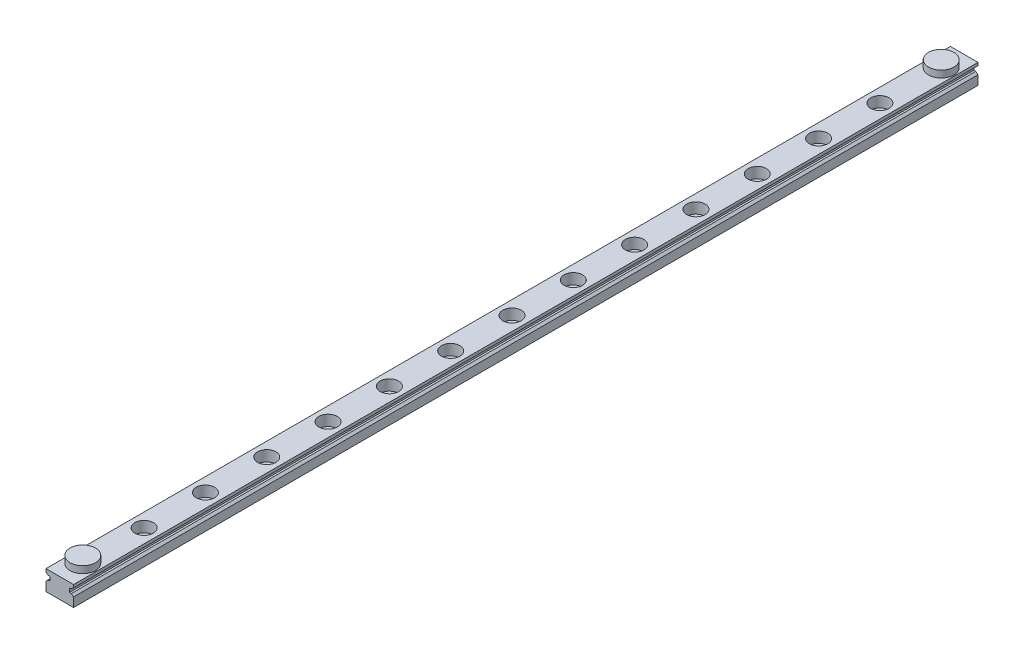
SolidWorks part; units mm, degrees
ref_plane "Front Plane" through (0, 0, 0) normal (0, 0, 1) x (1, 0, 0)
ref_plane "Top Plane" through (0, 0, 0) normal (0, 1, 0) x (1, 0, 0)
ref_plane "Right Plane" through (0, 0, 0) normal (1, 0, 0) x (0, 0, -1)
sketch "Sketch1" plane through (0, 0, 0) normal (0, 0, 1) x (1, 0, 0)
  line L0 (0, 0) -> (0, 13.8694) construction
  line L1 (4.5, 0) -> (-4.5, 0)
  line L2 (-4.5, 0) -> (-4.5, 3)
  line L3 (-3.7759, 3.6076) -> (-3.1688, 3.6076)
  line L4 (-3.1688, 3.6076) -> (-3.1688, 4.95)
  line L5 (-3.1688, 4.95) -> (-3.7759, 4.95)
  line L6 (-4.5, 5.5576) -> (-4.5, 6.5)
  line L7 (-4.5, 6.5) -> (0, 6.5)
  line L8 (-4.5, 5.5576) -> (-3.7759, 4.95)
  line L9 (-4.5, 3) -> (-3.7759, 3.6076)
  line L10 (-4.5, 4.95) -> (-4.5, 5.5576) construction
  line L11 (-3.7759, 4.95) -> (-4.5, 4.95) construction
  line L12 (-4.5, 3) -> (-4.5, 3.6076) construction
  line L13 (-4.5, 3.6076) -> (-3.7759, 3.6076) construction
  line L14 (-3.7759, 4.95) -> (-3.7759, 3.6076) construction
  line L15 (3.7759, 4.95) -> (3.7759, 3.6076) construction
  line L16 (4.5, 3.6076) -> (3.7759, 3.6076) construction
  line L17 (4.5, 3) -> (4.5, 3.6076) construction
  line L18 (3.7759, 4.95) -> (4.5, 4.95) construction
  line L19 (4.5, 4.95) -> (4.5, 5.5576) construction
  line L26 (4.5, 3) -> (3.7759, 3.6076)
  line L27 (4.5, 5.5576) -> (3.7759, 4.95)
  line L28 (4.5, 6.5) -> (0, 6.5)
  line L29 (4.5, 5.5576) -> (4.5, 6.5)
  line L30 (3.1688, 4.95) -> (3.7759, 4.95)
  line L31 (3.1688, 3.6076) -> (3.1688, 4.95)
  line L32 (3.7759, 3.6076) -> (3.1688, 3.6076)
  line L33 (4.5, 0) -> (4.5, 3)
  line L34 (-3, 6.5) -> (-3, 0) construction
  point P21 (-2.25, 6.5)
  point P34 (2.25, 6.5)
  dimension "D1" = 6.5
  dimension "D2" = 3
  dimension "D3" = 1.55
  dimension "D4" = 4.5
  dimension "D5" = 40
  dimension "D6" = 3.5
extrude "Boss-Extrude1" add sketch "Sketch1" along normal blind 295
sketch "Sketch2" plane through (0, 6.5, 0) normal (0, 1, 0) x (1, 0, 0)
  line L0 (0, 0) -> (0, -7.5) construction
  line L1 (4.5, 0) -> (-4.5, 0) construction
  circle A0 centre (0, -7.5) radius 3
  circle A1 centre (0, -7.5) radius 1.75
  dimension "D1" = 6
  dimension "D3" = 3.5
  dimension "D2" = 7.5
extrude "Cut-Extrude1" cut sketch "Sketch2" against normal through all contours A1
extrude "Cut-Extrude2" cut sketch "Sketch2<3>" against normal blind 3.5
sketch "Sketch2<3>" plane through (0, 6.5, 0) normal (0, 1, 0) x (1, 0, 0) same geometry as "Sketch2"
pattern_linear "LPattern1" count 15 spacing 20 along (0, 0, 1) of "Cut-Extrude1", "Cut-Extrude2"
sketch "Sketch4" plane through (0, 6.5, 0) normal (0, 1, 0) x (1, 0, 0)
  circle A0 centre (0, -7.5) radius 4.15
  point P0 (0, -7.5)
  dimension "D1" = 8.3
extrude "Boss-Extrude2" add sketch "Sketch4" along normal blind 2.25
pattern_linear "LPattern2" count 2 spacing 280 along (0, 0, 1) of "Boss-Extrude2"
